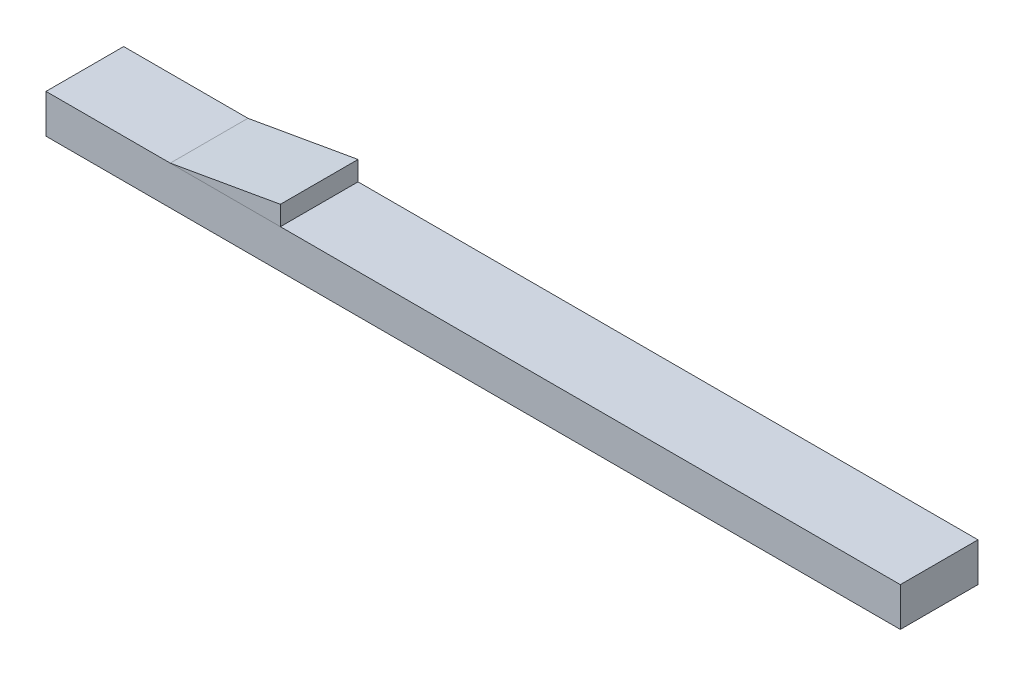
SolidWorks part; units mm, degrees
ref_plane "Front Plane" through (0, 0, 0) normal (0, 0, 1) x (1, 0, 0)
ref_plane "Top Plane" through (0, 0, 0) normal (0, 1, 0) x (1, 0, 0)
ref_plane "Right Plane" through (0, 0, 0) normal (1, 0, 0) x (0, 0, -1)
sketch "Sketch1" plane through (0, 0, 0) normal (0, 1, 0) x (1, 0, 0)
  line L1 (-34.925, -3.175) -> (34.925, -3.175)
  line L2 (-34.925, -3.175) -> (-34.925, 3.175)
  line L3 (-34.925, 3.175) -> (34.925, 3.175)
  line L4 (34.925, -3.175) -> (34.925, 3.175)
  line L5 (-34.925, -3.175) -> (34.925, 3.175) construction
  line L6 (-34.925, 3.175) -> (34.925, -3.175) construction
  point P0 (0, 0)
  dimension "D1" = 6.35
  dimension "D2" = 69.85
extrude "Boss-Extrude1" add sketch "Sketch1" along normal blind 3.175
sketch "Sketch2" plane through (0, 0, 3.175) normal (0, 0, 1) x (1, 0, 0)
  line L0 (-24.765, 3.175) -> (-15.7618, 4.7625)
  line L1 (-34.925, 3.175) -> (34.925, 3.175) construction
  line L2 (-15.7618, 4.7625) -> (-15.7618, 3.175)
  line L3 (-15.7618, 3.175) -> (-24.765, 3.175)
  dimension "D1" = 10.16
  dimension "D2" = 1.5875
  dimension "D3" = 80
extrude "Boss-Extrude2" add sketch "Sketch2" against normal blind 6.35 separate body
